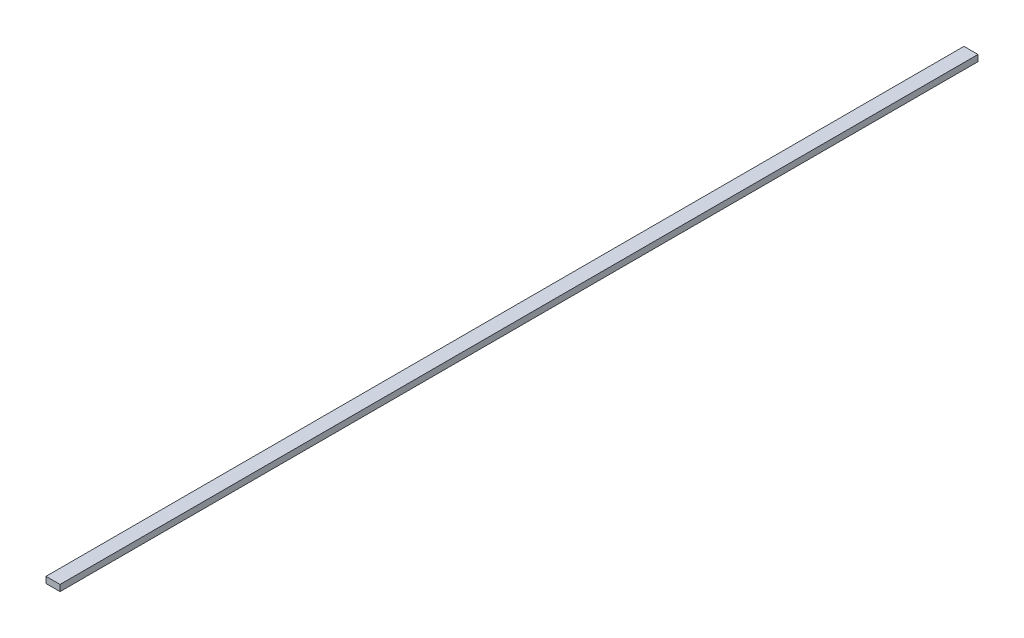
SolidWorks part; units mm, degrees
ref_plane "Front Plane" through (0, 0, 0) normal (1, 0, 0) x (0, 1, 0)
ref_plane "Top Plane" through (0, 0, 0) normal (0, 0, 1) x (0, 1, 0)
ref_plane "Right Plane" through (0, 0, 0) normal (0, 1, 0) x (-1, 0, 0)
sketch "Sketch1" plane through (0, 0, 0) normal (0, 0, 1) x (0, 1, 0)
  line L1 (-8.3312, -18.6436) -> (8.3312, -18.6436)
  line L2 (-8.3312, -18.6436) -> (-8.3312, 18.6436)
  line L3 (-8.3312, 18.6436) -> (8.3312, 18.6436)
  line L4 (8.3312, -18.6436) -> (8.3312, 18.6436)
  line L5 (-8.3312, -18.6436) -> (8.3312, 18.6436) construction
  line L6 (-8.3312, 18.6436) -> (8.3312, -18.6436) construction
  point P0 (0, 0)
  dimension "D1" = 16.6624
  dimension "D2" = 37.2872
extrude "Boss-Extrude1" add sketch "Sketch1" along normal mid plane 2438.4
